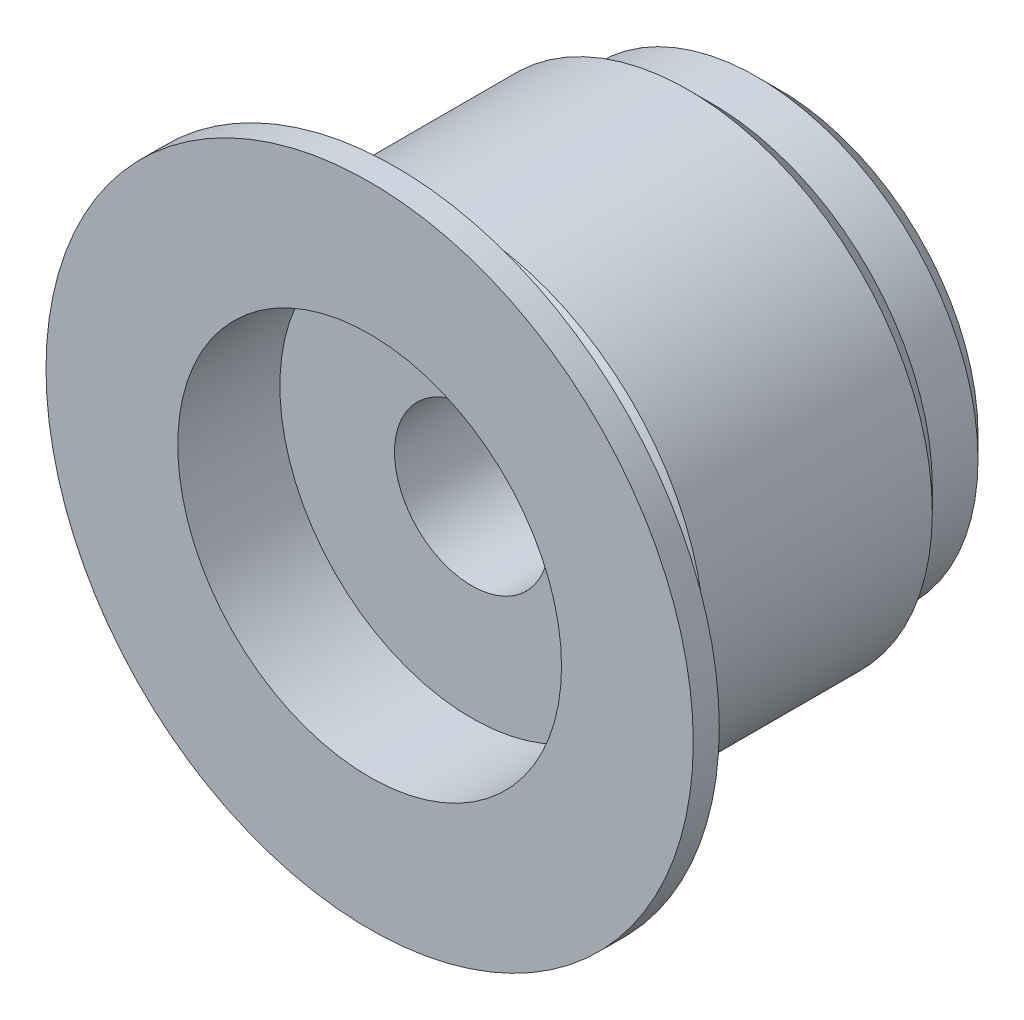
SolidWorks part; units mm, degrees
material "6061-T6 (SS)"
ref_plane "Front Plane" through (0, 0, 0) normal (0, 0, 1) x (1, 0, 0)
ref_plane "Top Plane" through (0, 0, 0) normal (0, 1, 0) x (1, 0, 0)
ref_plane "Right Plane" through (0, 0, 0) normal (1, 0, 0) x (0, 0, -1)
sketch "Sketch1" plane through (0, 0, 0) normal (0, 1, 0) x (1, 0, 0)
  line L1 (-12.6365, 0) -> (-12.6365, 1.016)
  line L3 (0, 16.002) -> (-9.525, 16.002) construction
  line L4 (-9.525, 16.002) -> (-9.525, 0) construction
  line L5 (-9.525, 12.446) -> (-9.525, 3.556)
  line L6 (-9.525, 12.446) -> (-8.627, 13.344)
  line L7 (-8.627, 13.344) -> (-8.627, 15.1277)
  line L8 (-8.627, 15.1277) -> (-7.7527, 16.002)
  line L9 (-7.7527, 16.002) -> (0, 16.002)
  line L10 (-9.525, 3.556) -> (-8.9618, 2.9928)
  line L11 (-8.9618, 2.9928) -> (-12.6365, 1.016)
  line L12 (0, 0) -> (-7.493, 0) construction
  line L13 (-7.493, 0) -> (-7.493, 3.9878)
  line L14 (0, 0) -> (0, 12.954) construction
  line L15 (0, 12.954) -> (-3.0162, 12.954) construction
  line L16 (-3.0162, 12.954) -> (-3.0162, 3.9878)
  line L17 (-3.0162, 3.9878) -> (-7.493, 3.9878)
  line L18 (-3.0162, 12.954) -> (0, 14.7663)
  line L19 (-12.6365, 0) -> (-7.493, 0)
  line L20 (0, 16.002) -> (0, 14.7663)
  point P10 (-9.525, 8.001)
  dimension "D1" = 12.6365
  dimension "D2" = 1.016
  dimension "D3" = 16.002
  dimension "D4" = 9.525
  dimension "D5" = 8.89
  dimension "D6" = 45
  dimension "D7" = 12.954
  dimension "D8" = 31
revolve "Revolve1" add sketch "Sketch1" angle 360 about L14
sketch "Sketch2" plane through (0, 0, -16.002) normal (0, 0, -1) x (-1, 0, 0)
  line L0 (0, 0) -> (0, -8.627) construction
  line L1 (0.4445, -3.6905) -> (-0.4445, -3.6905)
  line L2 (-0.4445, -3.6905) -> (-0.4445, -8.7807)
  line L3 (-0.4445, -8.7807) -> (0.4445, -8.7807)
  line L4 (0.4445, -8.7807) -> (0.4445, -3.6905)
  circle A0 centre (0, 0) radius 8.627 construction
  point P6 (0, 0)
  point P9 (0, -4.3135)
  dimension "D1" = 0.889
extrude "Cut-Extrude1" cut sketch "Sketch2" against normal blind 0.254
